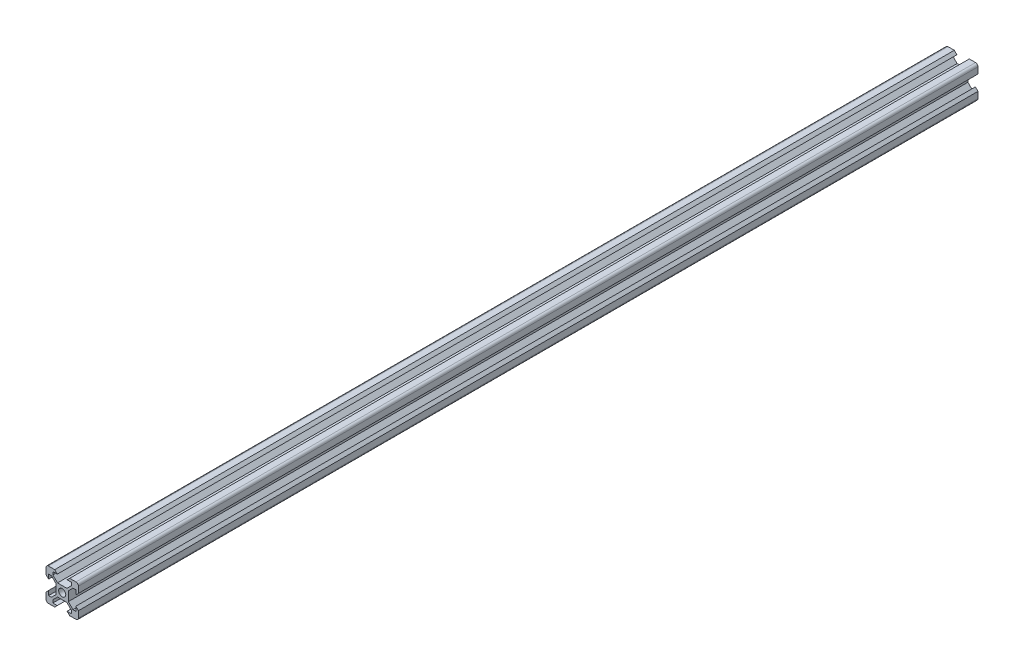
SolidWorks part; units mm, degrees
ref_plane "Front Plane" through (0, 0, 0) normal (0, 0, 1) x (1, 0, 0)
ref_plane "Top Plane" through (0, 0, 0) normal (0, 1, 0) x (1, 0, 0)
ref_plane "Right Plane" through (0, 0, 0) normal (1, 0, 0) x (0, 0, -1)
sketch "Sketch1" plane through (0, 0, 0) normal (0, 0, 1) x (1, 0, 0)
  line L0 (-5.7847, 7.544) -> (-11.512, 13.2713)
  line L1 (-7.544, 7.544) -> (7.544, 7.544)
  line L2 (-7.544, 7.544) -> (-7.544, -7.544)
  line L3 (-7.544, -7.544) -> (7.544, -7.544)
  line L4 (7.544, 7.544) -> (7.544, -7.544)
  line L5 (-7.544, 7.544) -> (7.544, -7.544) construction
  line L6 (-7.544, -7.544) -> (7.544, 7.544) construction
  line L7 (-11.512, 13.2713) -> (-11.512, 16.8)
  line L8 (-11.512, 16.8) -> (-6.052, 16.8)
  line L9 (-6.052, 16.8) -> (-9.252, 20)
  line L10 (-9.252, 20) -> (-17, 20)
  line L11 (-20, 17) -> (-20, 9.252)
  line L12 (-20, 9.252) -> (-16.8, 6.052)
  line L13 (-16.8, 6.052) -> (-16.8, 11.512)
  line L14 (-16.8, 11.512) -> (-13.2713, 11.512)
  line L15 (-13.2713, 11.512) -> (-7.544, 5.7847)
  line L16 (-19.1213, 19.1213) -> (0, 0) construction
  line L17 (13.2713, 11.512) -> (16.8, 11.512)
  line L18 (20, 9.252) -> (20, 17)
  line L19 (17, 20) -> (9.252, 20)
  line L20 (9.252, 20) -> (6.052, 16.8)
  line L21 (6.052, 16.8) -> (11.512, 16.8)
  line L22 (11.512, 16.8) -> (11.512, 13.2713)
  line L23 (11.512, 13.2713) -> (5.7847, 7.544)
  line L24 (7.544, 5.7847) -> (13.2713, 11.512)
  line L25 (16.8, 11.512) -> (16.8, 6.052)
  line L26 (16.8, 6.052) -> (20, 9.252)
  line L27 (19.1213, 19.1213) -> (0, 0) construction
  line L28 (11.512, -13.2713) -> (11.512, -16.8)
  line L29 (9.252, -20) -> (17, -20)
  line L30 (20, -17) -> (20, -9.252)
  line L31 (20, -9.252) -> (16.8, -6.052)
  line L32 (16.8, -6.052) -> (16.8, -11.512)
  line L33 (16.8, -11.512) -> (13.2713, -11.512)
  line L34 (13.2713, -11.512) -> (7.544, -5.7847)
  line L35 (5.7847, -7.544) -> (11.512, -13.2713)
  line L36 (11.512, -16.8) -> (6.052, -16.8)
  line L37 (6.052, -16.8) -> (9.252, -20)
  line L38 (19.1213, -19.1213) -> (0, 0) construction
  line L39 (-13.2713, -11.512) -> (-16.8, -11.512)
  line L40 (-20, -9.252) -> (-20, -17)
  line L41 (-17, -20) -> (-9.252, -20)
  line L42 (-9.252, -20) -> (-6.052, -16.8)
  line L43 (-6.052, -16.8) -> (-11.512, -16.8)
  line L44 (-11.512, -16.8) -> (-11.512, -13.2713)
  line L45 (-11.512, -13.2713) -> (-5.7847, -7.544)
  line L46 (-7.544, -5.7847) -> (-13.2713, -11.512)
  line L47 (-16.8, -11.512) -> (-16.8, -6.052)
  line L48 (-16.8, -6.052) -> (-20, -9.252)
  line L49 (-19.1213, -19.1213) -> (0, 0) construction
  circle A0 centre (0, 0) radius 4.4
  arc A1 (-17, 20) -> (-20, 17) centre (-17, 17) ccw
  arc A2 (20, 17) -> (17, 20) centre (17, 17) ccw
  arc A3 (17, -20) -> (20, -17) centre (17, -17) ccw
  arc A4 (-20, -17) -> (-17, -20) centre (-17, -17) ccw
  point P66 (0, 0)
  dimension "D1" = 8.8
  dimension "D8" = 3
  dimension "D2" = 15.088
  dimension "D3" = 2.488
  dimension "D4" = 8.488
  dimension "D5" = 3.2
  dimension "D6" = 20
  dimension "D7" = 15.2
  dimension "D9" = 4
extrude "Boss-Extrude1" add sketch "Sketch1" along normal mid plane 1110 contours L10 A1 L11 L12 L13 L14 L15 L2 L1 L0 L7 L8 L9 | L18 A2 L19 L20 L21 L22 L23 L1 L4 L24 L17 L25 L26 | L40 A4 L41 L42 L43 L44 L45 L3 L2 L46 L39 L47 L48 | L29 A3 L30 L31 L32 L33 L34 L4 L3 L35 L28 L36 L37 | L4 L1 L2 L3 A0 region at (-14.3184, 14.3184, 0) region at (0, 7.3306, 0) region at (14.3184, 14.3184, 0) region at (-14.3184, -14.3184, 0) region at (14.3184, -14.3184, 0)
equation "\"longitud\"= 800"
